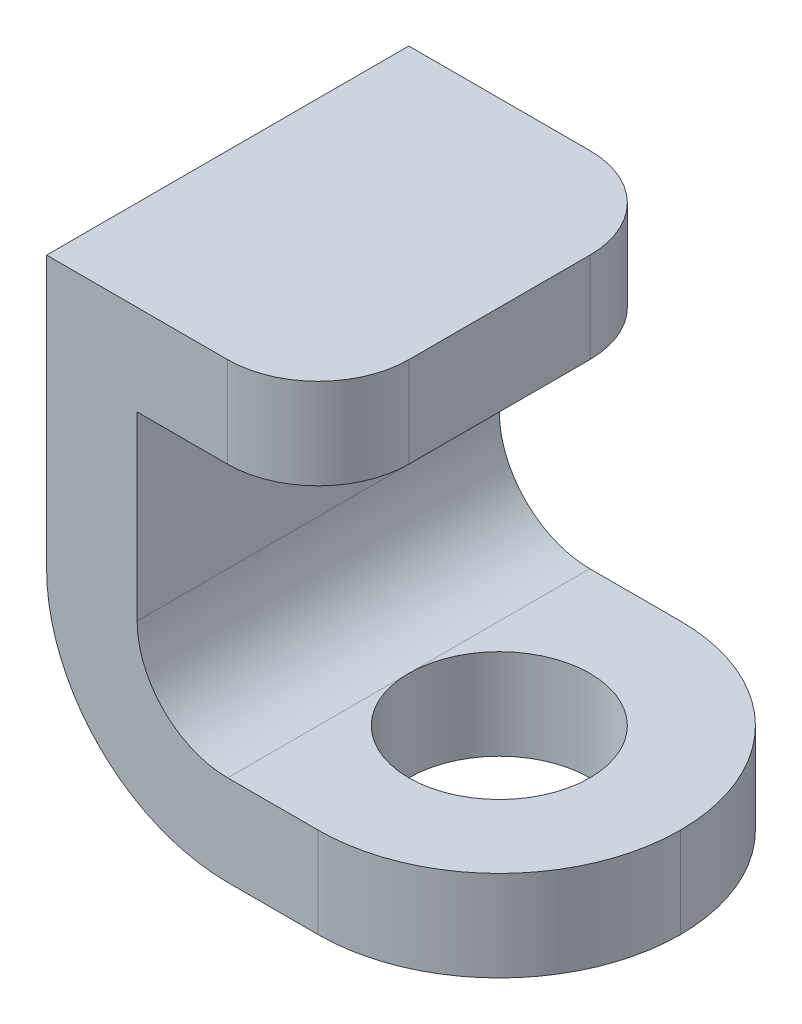
SolidWorks part; units mm, degrees
ref_plane "前基準面" through (0, 0, 0) normal (0, 0, 1) x (1, 0, 0)
ref_plane "上基準面" through (0, 0, 0) normal (0, 1, 0) x (1, 0, 0)
ref_plane "右基準面" through (0, 0, 0) normal (1, 0, 0) x (0, 0, -1)
sketch "草圖2" plane through (0, 0, 0) normal (0, 0, 1) x (1, 0, 0)
  line L1 (0, 0) -> (15, 0)
  line L2 (0, 0) -> (0, -5)
  line L3 (0, -5) -> (15, -5)
  line L4 (15, 0) -> (15, -5)
  line L5 (0, 0) -> (5, 0)
  line L6 (0, 0) -> (0, -20)
  line L7 (0, -20) -> (5, -20)
  line L8 (5, 0) -> (5, -20)
  line L9 (0, -20) -> (25, -20)
  line L10 (0, -20) -> (0, -25)
  line L11 (0, -25) -> (25, -25)
  line L12 (25, -20) -> (25, -25)
  dimension "D1" = 5
  dimension "D2" = 5
  dimension "D3" = 5
  dimension "D4" = 25
  dimension "D5" = 15
  dimension "D6" = 20
extrude "填料-伸長1" add sketch "草圖2" against normal blind 20 contours L8 L1 L2 L3 | L1 L8 L3 L4 | L8 L3 L6 L7 | L12 L9 L7 L10 L11 region at (2.5, -2.5, 0) region at (10, -2.5, 0) region at (2.5, -12.5, 0) region at (12.5, -22.5, 0)
fillet "圓角1" radius 10 3 edges at (25, -22.5, -20) (25, -22.5, 0) (0, -25, -10)
fillet "圓角2" radius 5 3 edges at (5, -20, -10) (15, -2.5, -20) (15, -2.5, 0)
sketch "草圖3" plane through (0, -20, 0) normal (0, 1, 0) x (1, 0, 0)
  line L0 (15, 15) -> (15, 5) construction
  circle A0 centre (15, 10) radius 5
  dimension "D1" = 10
extrude "除料-伸長1" cut sketch "草圖3" against normal through all
